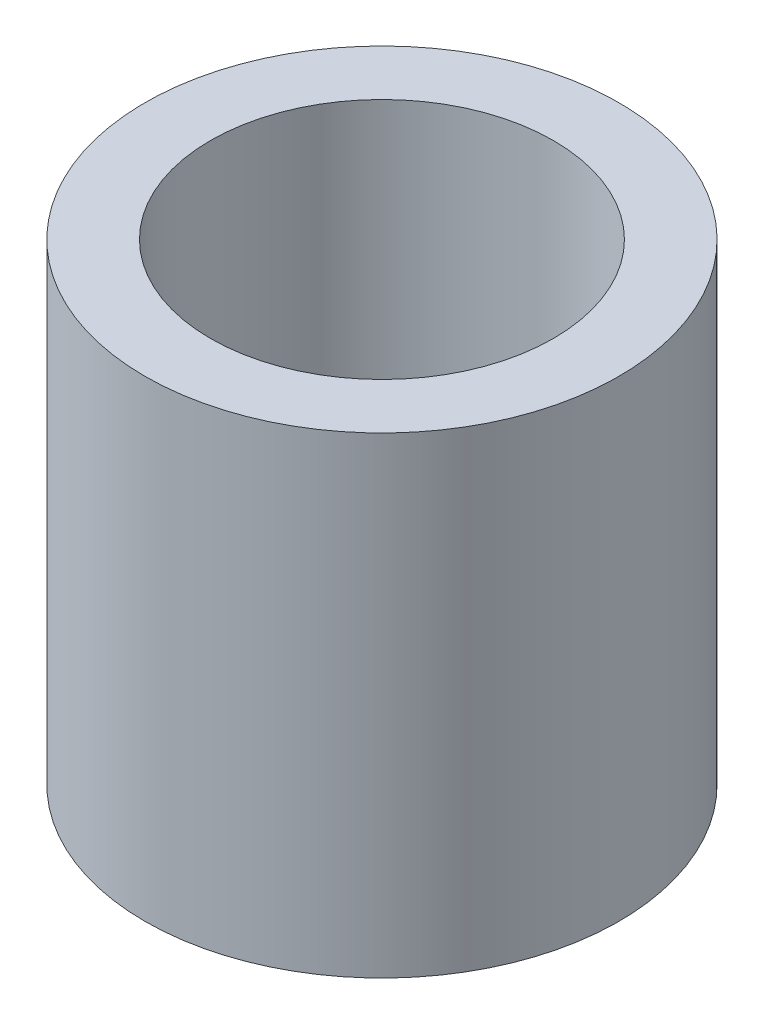
SolidWorks part; units mm, degrees
ref_plane "Front Plane" through (0, 0, 0) normal (0, 0, 1) x (1, 0, 0)
ref_plane "Top Plane" through (0, 0, 0) normal (0, 1, 0) x (1, 0, 0)
ref_plane "Right Plane" through (0, 0, 0) normal (1, 0, 0) x (0, 0, -1)
sketch "Sketch1" plane through (0, 0, 0) normal (0, 1, 0) x (1, 0, 0)
  circle A0 centre (0, 0) radius 12.3
  dimension "D1" = 24.6
extrude "Boss-Extrude1" add sketch "Sketch1" along normal blind 24.5
sketch "Sketch2" plane through (0, 24.5, 0) normal (0, 1, 0) x (1, 0, 0)
  circle A0 centre (0, 0) radius 8.9
  circle A1 centre (0, 0) radius 12.3 construction
  dimension "D1" = 3.4
extrude "Cut-Extrude1" cut sketch "Sketch2" against normal blind 20
sketch "Sketch3" plane through (0, 4.5, 0) normal (0, 1, 0) x (1, 0, 0)
  circle A0 centre (0, 0) radius 5.5
  dimension "D1" = 11
extrude "Cut-Extrude2" cut sketch "Sketch3" against normal blind 1
sketch "Sketch4" plane through (0, 3.5, 0) normal (0, 1, 0) x (1, 0, 0)
  circle A0 centre (0, 0) radius 4.3
  dimension "D1" = 8.6
extrude "Cut-Extrude3" cut sketch "Sketch4" against normal up to next
